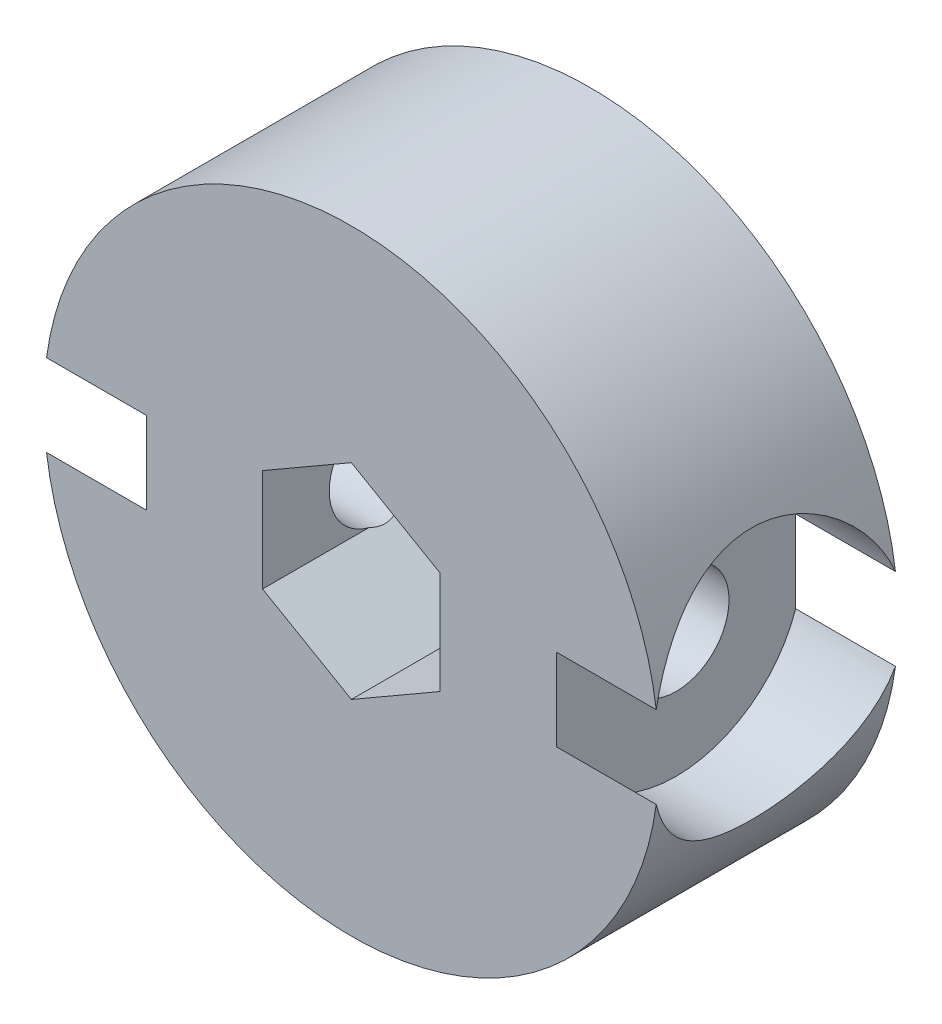
SolidWorks part; units mm, degrees
ref_plane "Front Plane" through (0, 0, 0) normal (0, 0, 1) x (1, 0, 0)
ref_plane "Top Plane" through (0, 0, 0) normal (0, 1, 0) x (1, 0, 0)
ref_plane "Right Plane" through (0, 0, 0) normal (1, 0, 0) x (0, 0, -1)
sketch "Sketch1" plane through (0, 0, 0) normal (0, 0, 1) x (1, 0, 0)
  line L0 (0, -3) -> (0, 3) construction
  line L1 (-2.5981, -1.5) -> (2.5981, 1.5) construction
  line L2 (-2.5981, 1.5) -> (2.5981, -1.5) construction
  line L3 (0, 3) -> (2.5981, 1.5)
  line L4 (2.5981, 1.5) -> (2.5981, -1.5)
  line L5 (2.5981, -1.5) -> (0, -3)
  line L6 (0, -3) -> (-2.5981, -1.5)
  line L7 (-2.5981, -1.5) -> (-2.5981, 1.5)
  line L8 (-2.5981, 1.5) -> (0, 3)
  circle A0 centre (0, 0) radius 9
  circle A2 centre (0, 0) radius 3 construction
  point P7 (0, 0)
  point P9 (0, 0)
  point P13 (0, 0)
  point P14 (0, 0)
extrude "Boss-Extrude1" add sketch "Sketch1" along normal blind 7
ref_plane "Plane1" through (0, 0, 0) normal (-1, 0, 0) x (0, 0, 1)
sketch "Sketch5" plane through (0, 0, 0) normal (-1, 0, 0) x (0, 0, 1)
  line L0 (7, -9) -> (7, 9) construction
  line L1 (7, 0) -> (3.5, 0) construction
  circle A0 centre (3.5, 0) radius 1.55
  point P10 (7, 0)
extrude "Cut-Extrude1" cut sketch "Sketch5" against normal blind 9 and the other way blind 9
ref_plane "Plane2" through (-6, 0, 0) normal (-1, 0, 0) x (0, 0, 1)
ref_plane "Plane3" through (6, 0, 0) normal (-1, 0, 0) x (0, 0, 1)
sketch "Sketch6" plane through (-6, 0, 0) normal (-1, 0, 0) x (0, 0, 1)
  circle A0 centre (3.5, 0) radius 3.7
extrude "Cut-Extrude2" cut sketch "Sketch6" along normal blind 5.5
sketch "Sketch7" plane through (6, 0, 0) normal (-1, 0, 0) x (0, 0, 1)
  circle A0 centre (3.5, 0) radius 3.7
extrude "Cut-Extrude3" cut sketch "Sketch7" against normal blind 5.5 contours A0
